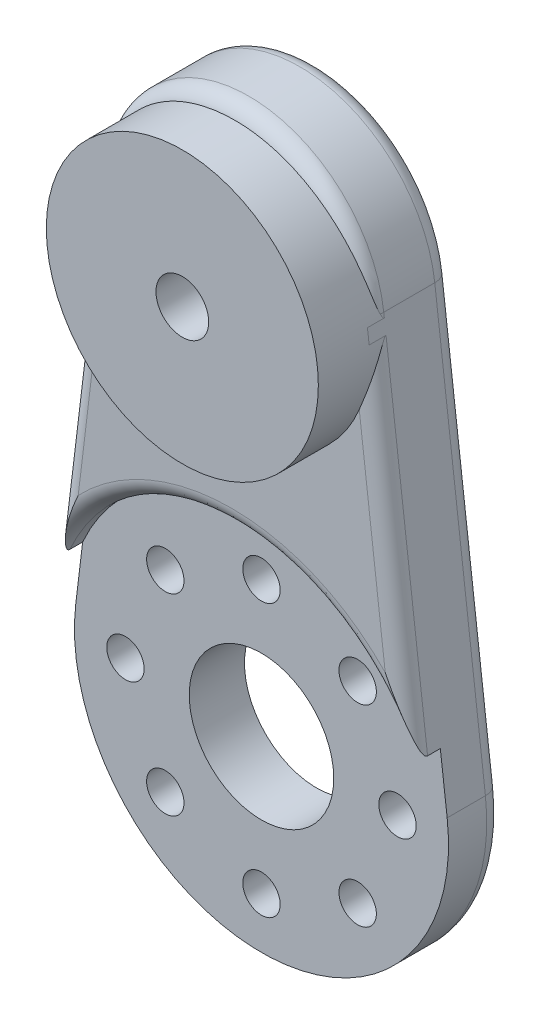
SolidWorks part; units mm, degrees
ref_plane "Front Plane" through (0, 0, 0) normal (0, 0, 1) x (1, 0, 0)
ref_plane "Top Plane" through (0, 0, 0) normal (0, 1, 0) x (1, 0, 0)
ref_plane "Right Plane" through (0, 0, 0) normal (1, 0, 0) x (0, 0, -1)
sketch "Sketch1" plane through (0, 0, 0) normal (0, 0, 1) x (1, 0, 0)
  line L0 (-22.9263, 5.5263) -> (-25.9047, -19.1137)
  line L3 (-7.042, 5.5263) -> (-4.0636, -19.1137)
  line L4 (-14.9841, 0.14) -> (-14.9841, 20.14) construction
  line L5 (-14.7274, -20.4337) -> (49985.2726, -20.4337) construction
  circle A2 centre (-14.9841, 4.5663) radius 1.55
  circle A3 centre (-14.9841, -20.4337) radius 4.25
  arc A5 (-7.042, 5.5263) -> (-22.9263, 5.5263) centre (-14.9841, 4.5663) ccw
  arc A6 (-25.9047, -19.1137) -> (-4.0636, -19.1137) centre (-14.9841, -20.4337) ccw
  circle A7 centre (-14.9369, -20.7787) radius 11 construction
  circle A8 centre (-6.9841, -20.4337) radius 1.1
  circle A9 centre (-9.3273, -26.0906) radius 1.1
  circle A10 centre (-14.9841, -28.4337) radius 1.1
  circle A11 centre (-20.641, -26.0906) radius 1.1
  circle A12 centre (-22.9841, -20.4337) radius 1.1
  circle A13 centre (-20.641, -14.7769) radius 1.1
  circle A14 centre (-14.9841, -12.4337) radius 1.1
  circle A15 centre (-9.3273, -14.7769) radius 1.1
  point P30 (-14.9841, -20.4337)
  dimension "D1" = 3.1
  dimension "D3" = 25
  dimension "D4" = 11
  dimension "D2" = 8
  dimension "D5" = 8.5
  dimension "D6" = 2.2
  dimension "D7" = 8
  dimension "D8" = 8
extrude "Boss-Extrude1" add sketch "Sketch1" along normal blind 5
sketch "Sketch2" plane through (0, 0, 5) normal (0, 0, 1) x (1, 0, 0)
  circle A0 centre (-14.9841, -20.4337) radius 11.5
  dimension "D1" = 23
extrude "Cut-Extrude1" cut sketch "Sketch2" against normal blind 1.75
sketch "Sketch3" plane through (0, 0, 0) normal (0, 0, 1) x (1, 0, 0)
  line L1 (-15.415, 7.7123) -> (-17.9242, 5.7661)
  line L2 (-17.9242, 5.7661) -> (-17.4933, 2.6201)
  line L3 (-17.4933, 2.6201) -> (-14.5533, 1.4202)
  line L4 (-14.5533, 1.4202) -> (-12.0441, 3.3664)
  line L5 (-12.0441, 3.3664) -> (-12.475, 6.5125)
  line L6 (-12.475, 6.5125) -> (-15.415, 7.7123)
  circle A0 centre (-14.9841, 4.5663) radius 2.75 construction
  dimension "D1" = 5.5
extrude "Cut-Extrude2" cut sketch "Sketch3" along normal blind 3
sketch "Sketch5" plane through (0, 0, 5) normal (0, 0, 1) x (1, 0, 0)
  circle A2 centre (-14.8897, 3.8764) radius 1.55
  circle A3 centre (-14.8897, 3.8764) radius 8
extrude "Boss-Extrude2" add sketch "Sketch5" along normal blind 3
fillet "Fillet1" radius 1 9 edges at (-5.5528, -6.7937, 0) (-14.9841, -31.4337, 0) (-14.9841, -8.9337, 5) (-14.9841, 12.5663, 0) (-24.4155, -6.7937, 0) (-5.6871, -5.6827, 5) (-7.0254, 5.389, 5) (-14.9841, 12.5663, 5) (-24.2142, -5.1288, 5)
sketch "Sketch4" plane through (0, 0, 0) normal (0, 0, -1) x (-1, 0, 0)
  circle A0 centre (22.9841, -20.4337) radius 1.75
  circle A1 centre (20.641, -26.0906) radius 1.75
  circle A2 centre (14.9841, -28.4337) radius 1.75
  circle A3 centre (9.3273, -26.0906) radius 1.75
  circle A4 centre (6.9841, -20.4337) radius 1.75
  circle A5 centre (9.3273, -14.7769) radius 1.75
  circle A6 centre (14.9841, -12.4337) radius 1.75
  circle A7 centre (20.641, -14.7769) radius 1.75
  circle A10 centre (14.9841, -20.4337) radius 4.25 construction
  point P20 (14.9841, -20.4337)
  dimension "D1" = 3.5
extrude "Cut-Extrude3" [suppressed] cut sketch "Sketch4" against normal blind 0.5
